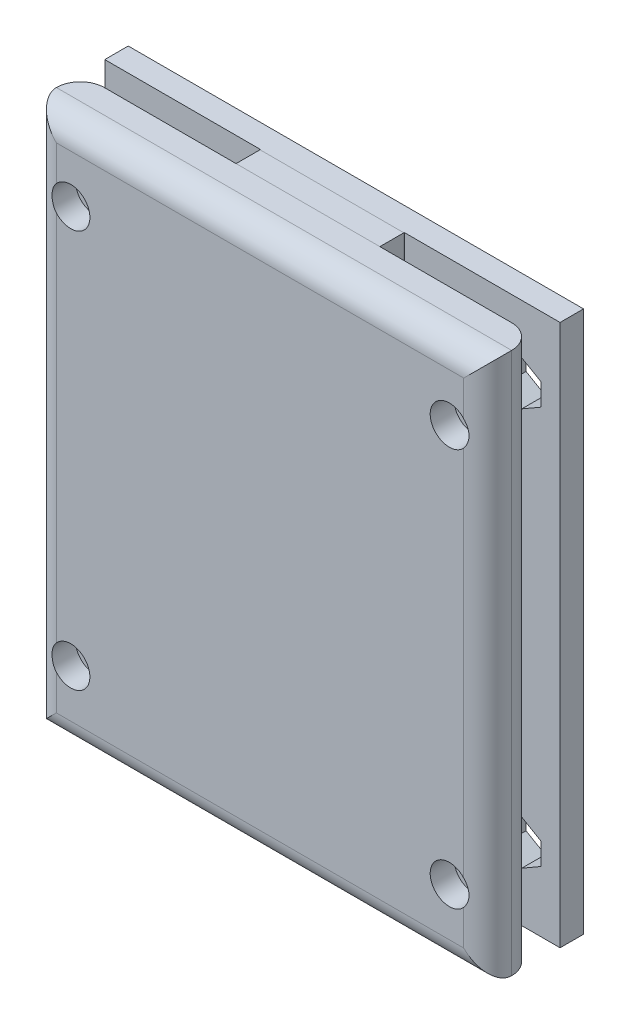
SolidWorks part; units mm, degrees
ref_plane "Alzado" through (0, 0, 0) normal (0, 0, 1) x (1, 0, 0)
ref_plane "Planta" through (0, 0, 0) normal (0, 1, 0) x (1, 0, 0)
ref_plane "Vista lateral" through (0, 0, 0) normal (1, 0, 0) x (0, 0, -1)
sketch "Croquis1" plane through (0, 0, 0) normal (0, 0, 1) x (1, 0, 0)
  line L0 (0, 56.5) -> (0, -56.5) construction
  line L1 (-47.5, -56.5) -> (47.5, -56.5)
  line L2 (-47.5, -56.5) -> (-47.5, 56.5)
  line L3 (-47.5, 56.5) -> (47.5, 56.5)
  line L4 (47.5, -56.5) -> (47.5, 56.5)
  line L5 (-47.5, -56.5) -> (47.5, 56.5) construction
  line L6 (-47.5, 56.5) -> (47.5, -56.5) construction
  line L7 (-35.5, 39.1906) -> (-35.5, 43.8094)
  line L8 (-35.5, 43.8094) -> (-39.5, 46.1188)
  line L9 (-39.5, 46.1188) -> (-43.5, 43.8094)
  line L10 (-43.5, 43.8094) -> (-43.5, 39.1906)
  line L11 (-43.5, 39.1906) -> (-39.5, 36.8812)
  line L12 (-39.5, 36.8812) -> (-35.5, 39.1906)
  line L13 (-35.5, -43.8094) -> (-35.5, -39.1906)
  line L14 (-35.5, -39.1906) -> (-39.5, -36.8812)
  line L15 (-39.5, -36.8812) -> (-43.5, -39.1906)
  line L16 (-43.5, -39.1906) -> (-43.5, -43.8094)
  line L17 (-43.5, -43.8094) -> (-39.5, -46.1188)
  line L18 (-39.5, -46.1188) -> (-35.5, -43.8094)
  line L19 (39.5, -46.1188) -> (35.5, -43.8094)
  line L20 (43.5, -43.8094) -> (39.5, -46.1188)
  line L21 (43.5, -39.1906) -> (43.5, -43.8094)
  line L22 (39.5, -36.8812) -> (43.5, -39.1906)
  line L23 (35.5, -39.1906) -> (39.5, -36.8812)
  line L24 (35.5, -43.8094) -> (35.5, -39.1906)
  line L25 (39.5, 36.8812) -> (35.5, 39.1906)
  line L26 (43.5, 39.1906) -> (39.5, 36.8812)
  line L27 (43.5, 43.8094) -> (43.5, 39.1906)
  line L28 (39.5, 46.1188) -> (43.5, 43.8094)
  line L29 (35.5, 43.8094) -> (39.5, 46.1188)
  line L30 (35.5, 39.1906) -> (35.5, 43.8094)
  circle A0 centre (-39.5, 41.5) radius 4 construction
  circle A1 centre (-39.5, -41.5) radius 4 construction
  circle A2 centre (39.5, -41.5) radius 4 construction
  circle A3 centre (39.5, 41.5) radius 4 construction
  point P0 (0, 0)
  dimension "D1" = 113
  dimension "D2" = 95
  dimension "D3" = 8
  dimension "D4" = 8
  dimension "D5" = 15
  dimension "D6" = 15
  dimension "D7" = 8
  dimension "D8" = 8
extrude "Saliente-Extruir1" add sketch "Croquis1" along normal blind 5
sketch "Croquis2" plane through (0, 0, 5) normal (0, 0, 1) x (1, 0, 0)
  line L0 (47.5, 56.5) -> (-47.5, 56.5) construction
  line L1 (-15, -56.5) -> (15, -56.5)
  line L2 (-15, -56.5) -> (-15, 56.5)
  line L3 (-15, 56.5) -> (15, 56.5)
  line L4 (15, -56.5) -> (15, 56.5)
  line L5 (-15, -56.5) -> (15, 56.5) construction
  line L6 (-15, 56.5) -> (15, -56.5) construction
  point P0 (0, 0)
  dimension "D1" = 30
extrude "Saliente-Extruir2" add sketch "Croquis2" along normal blind 5
sketch "Croquis3" plane through (0, 0, 10) normal (0, 0, 1) x (1, 0, 0)
  line L1 (-47.5, 56.5) -> (47.5, 56.5)
  line L2 (-47.5, 56.5) -> (-47.5, -56.5)
  line L3 (-47.5, -56.5) -> (47.5, -56.5)
  line L4 (47.5, 56.5) -> (47.5, -56.5)
extrude "Saliente-Extruir3" add sketch "Croquis3" along normal blind 10
sketch "Croquis4" plane through (0, 0, 20) normal (0, 0, 1) x (1, 0, 0)
  line L0 (-43.5, -39.1906) -> (-43.5, -43.8094) construction
  line L1 (-35.5, -43.8094) -> (-35.5, -39.1906) construction
  line L2 (35.5, -39.1906) -> (35.5, -43.8094) construction
  line L3 (43.5, -43.8094) -> (43.5, -39.1906) construction
  line L4 (43.5, 39.1906) -> (43.5, 43.8094) construction
  line L5 (35.5, 43.8094) -> (35.5, 39.1906) construction
  line L6 (-35.5, 39.1906) -> (-35.5, 43.8094) construction
  line L7 (-43.5, 43.8094) -> (-43.5, 39.1906) construction
  line L8 (-43.5, -39.1906) -> (-43.5, -43.8094) construction
  line L9 (-35.5, -43.8094) -> (-35.5, -39.1906) construction
  line L10 (35.5, -39.1906) -> (35.5, -43.8094) construction
  line L11 (43.5, -43.8094) -> (43.5, -39.1906) construction
  line L12 (43.5, 39.1906) -> (43.5, 43.8094) construction
  line L13 (35.5, 43.8094) -> (35.5, 39.1906) construction
  line L14 (-35.5, 39.1906) -> (-35.5, 43.8094) construction
  line L15 (-43.5, 43.8094) -> (-43.5, 39.1906) construction
  line L16 (-43.5, 41.5) -> (-35.5, 41.5) construction
  line L17 (-43.5, -41.5) -> (-35.5, -41.5) construction
  line L18 (35.5, -41.5) -> (43.5, -41.5) construction
  line L19 (35.5, 41.5) -> (43.5, 41.5) construction
  circle A0 centre (39.5, 41.5) radius 4
  circle A1 centre (-39.5, 41.5) radius 4
  circle A2 centre (-39.5, -41.5) radius 4
  circle A3 centre (39.5, -41.5) radius 4
  dimension "D1" = 8
  dimension "D2" = 8
  dimension "D3" = 8
  dimension "D4" = 8
extrude "Cortar-Extruir3" cut sketch "Croquis4" against normal blind 5 and the other way through all
sketch "Croquis5" plane through (0, 0, 20) normal (0, 0, 1) x (1, 0, 0)
  circle A2 centre (-39.5, 41.5) radius 2.5
  circle A3 centre (-39.5, 41.5) radius 2.5
  circle A14 centre (39.5, 41.5) radius 2.5
  circle A15 centre (39.5, 41.5) radius 2.5
  circle A17 centre (-39.5, -41.5) radius 2.5
  circle A18 centre (-39.5, -41.5) radius 2.5
  circle A20 centre (39.5, -41.5) radius 2.5
  circle A21 centre (39.5, -41.5) radius 2.5
  dimension "D1" = 1.5
  dimension "D2" = 1.5
  dimension "D3" = 1.5
  dimension "D4" = 1.5
extrude "Cortar-Extruir7" cut sketch "Croquis5" against normal through all
fillet "Redondeo3" radius 5 4 edges at (0, 56.5, 20) (47.5, 0, 20) (0, -56.5, 20) (-47.5, 0, 20)
fillet "Redondeo2" radius 5 2 edges at (47.5, 0, 10) (-47.5, 0, 10)
sketch "Croquis6" plane through (0, 0, 5) normal (0, 0, 1) x (1, 0, 0)
  line L0 (-15, 56.5) -> (-15, -56.5) construction
  line L1 (15, -56.5) -> (15, 56.5) construction
  line L2 (-15, 56.5) -> (-15, -56.5)
  line L3 (15, -56.5) -> (15, 56.5)
  line L4 (47.5, -56.5) -> (47.5, 56.5)
  line L5 (47.5, 56.5) -> (-47.5, 56.5)
  line L6 (-47.5, 56.5) -> (-47.5, -56.5)
  line L7 (-47.5, -56.5) -> (47.5, -56.5)
  line L8 (47.5, -56.5) -> (47.5, 56.5)
  line L9 (47.5, 56.5) -> (15, 56.5)
  line L10 (-47.5, 56.5) -> (-47.5, -56.5)
  line L11 (-47.5, -56.5) -> (-15, -56.5)
  line L12 (-15, 56.5) -> (-47.5, 56.5)
  line L13 (15, -56.5) -> (47.5, -56.5)
  dimension "D1" = 0
extrude "Cortar-Extruir8" cut sketch "Croquis6" against normal blind 0.1
